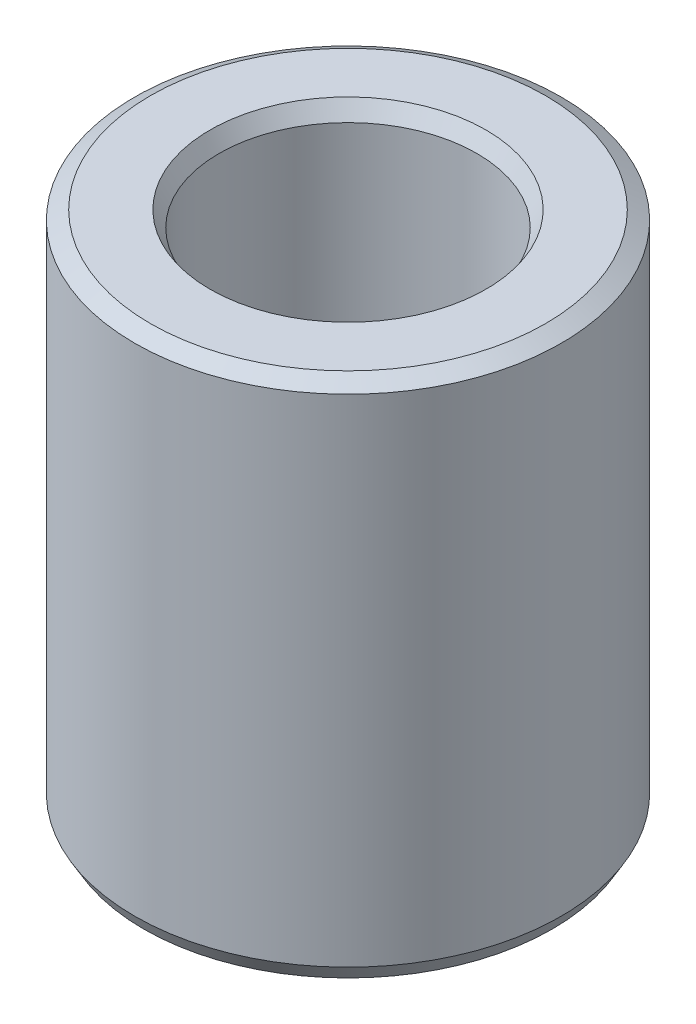
SolidWorks part; units mm, degrees
ref_plane "Front Plane" through (0, 0, 0) normal (0, 0, 1) x (1, 0, 0)
ref_plane "Top Plane" through (0, 0, 0) normal (0, 1, 0) x (1, 0, 0)
ref_plane "Right Plane" through (0, 0, 0) normal (1, 0, 0) x (0, 0, -1)
sketch "Sketch1" plane through (0, 0, 0) normal (0, 1, 0) x (1, 0, 0)
  circle A0 centre (0, 0) radius 47.5
  dimension "SLEEVE_OD" = 95
extrude "Boss-Extrude1" add sketch "Sketch1" along normal blind 116.0425
sketch "Sketch2" plane through (0, 0, 0) normal (0, 1, 0) x (1, 0, 0)
  circle A0 centre (0, 0) radius 28.7036
  dimension "BORE_D" = 57.4073
extrude "Cut-Extrude1" cut sketch "Sketch2" along normal through all
chamfer "Chamfer1" distance 2.0279 angle 60 4 edges at (0, 116.0425, 28.7036) (0, 0, 28.7036) (0, 0, 47.5) (0, 116.0425, 47.5) first distance on face at (0, 116.0425, 28.7036) first distance on face at (0, 0, 28.7036) first distance on face at (0, 116.0425, 47.5)
